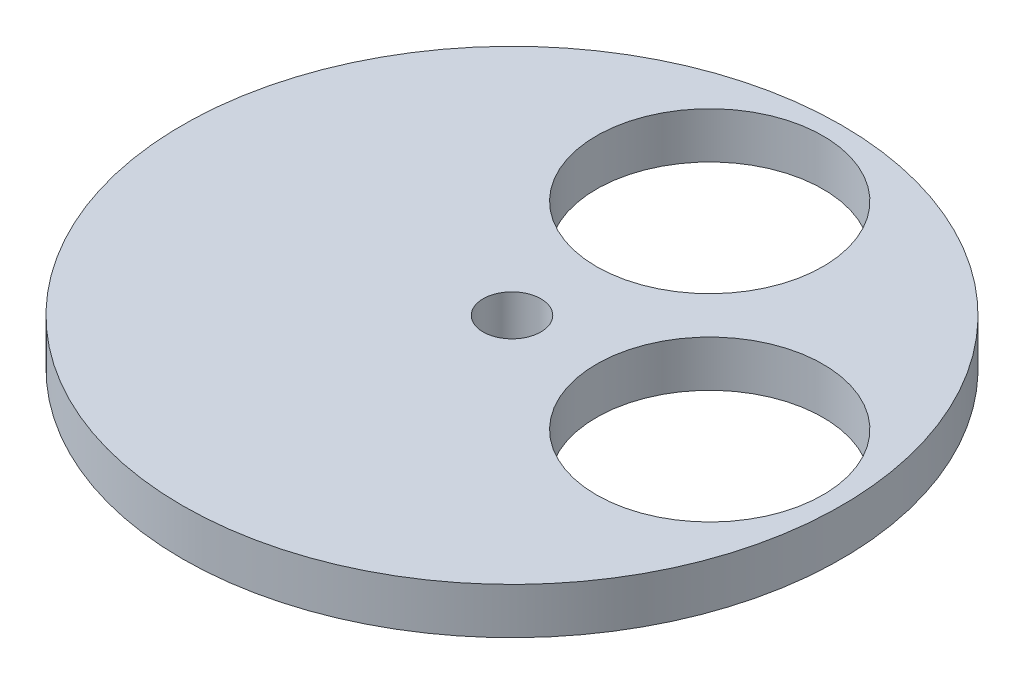
SolidWorks part; units mm, degrees
ref_plane "Front Plane" through (0, 0, 0) normal (0, 0, 1) x (1, 0, 0)
ref_plane "Top Plane" through (0, 0, 0) normal (0, 1, 0) x (1, 0, 0)
ref_plane "Right Plane" through (0, 0, 0) normal (1, 0, 0) x (0, 0, -1)
sketch "Sketch6" plane through (0, 0, 0) normal (0, 1, 0) x (1, 0, 0)
  circle A2 centre (63.5, 63.5) radius 50.8
  dimension "D1" = 101.6
extrude "Boss-Extrude3" add sketch "Sketch6" along normal blind 7.112 contours A2
sketch "Sketch11" plane through (0, 7.112, 0) normal (0, 1, 0) x (1, 0, 0)
  line L0 (63.5, 114.3) -> (63.5, 63.5)
  line L1 (63.5, 63.5) -> (114.3, 63.5)
  circle A0 centre (63.5, 93.98) radius 17.4625
  circle A1 centre (93.98, 63.5) radius 17.4625
  circle A2 centre (63.5, 63.5) radius 50.8 construction
  point P7 (0, 0)
  point P11 (0, 0)
  point P12 (0, 0)
  point P13 (0, 0)
  point P14 (0, 0)
  point P15 (0, 0)
  point P16 (0, 0)
  dimension "D1" = 34.925
  dimension "D4" = 34.925
  dimension "D2" = 20.32
  dimension "D3" = 20.32
extrude "Cut-Extrude2" cut sketch "Sketch11" against normal through all contours L0 A0 | L0 A0 | L1 A1 | L1 A1 | A0 region at (70.9113, 7.112, -93.98) region at (93.98, 7.112, -70.9113) region at (93.98, 7.112, -56.0887) region at (56.0887, 7.112, -93.98)
sketch "Sketch12" plane through (0, 7.112, 0) normal (0, 1, 0) x (1, 0, 0)
  circle A0 centre (63.5, 63.5) radius 4.445
  dimension "D1" = 8.89
extrude "Cut-Extrude3" cut sketch "Sketch12" against normal through all contours A0
